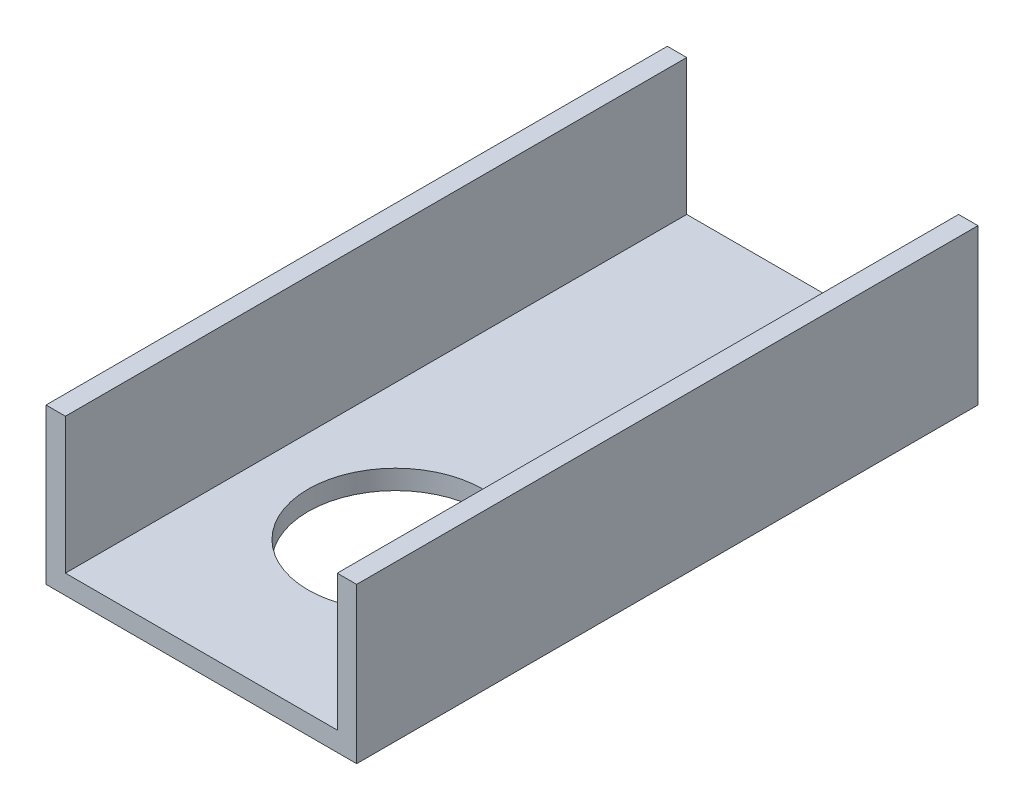
SolidWorks part; units mm, degrees
material "6063-T6"
ref_plane "Front" through (0, 0, 0) normal (0, 0, 1) x (1, 0, 0)
ref_plane "Top" through (0, 0, 0) normal (0, 1, 0) x (1, 0, 0)
ref_plane "Right" through (0, 0, 0) normal (1, 0, 0) x (0, 0, -1)
sketch "Sketch1" plane through (0, 0, 0) normal (0, 0, 1) x (1, 0, 0)
  line L0 (47.625, 3.175) -> (47.625, 25.4)
  line L1 (0, 0) -> (50.8, 0)
  line L2 (0, 0) -> (0, 25.4)
  line L4 (50.8, 0) -> (50.8, 25.4)
  line L5 (3.175, 3.175) -> (47.625, 3.175)
  line L6 (3.175, 3.175) -> (3.175, 25.4)
  line L7 (50.8, 25.4) -> (47.625, 25.4)
  line L8 (0, 25.4) -> (3.175, 25.4)
  dimension "D1" = 25.4
  dimension "D2" = 50.8
  dimension "D3" = 3.175
extrude "Boss-Extrude1" add sketch "Sketch1" along normal blind 101.6
sketch "Sketch2" plane through (0, 0, 0) normal (0, -1, 0) x (1, 0, 0)
  line L0 (25.4, 69.85) -> (25.4, 101.6) construction
  line L1 (0, 101.6) -> (50.8, 101.6) construction
  circle A0 centre (25.4, 69.85) radius 14.2875
  dimension "D1" = 28.575
  dimension "D2" = 31.75
extrude "Cut-Extrude1" cut sketch "Sketch2" against normal up to next
sketch "Sketch3" plane through (0, 3.175, 0) normal (0, 1, 0) x (1, 0, 0)
  line L1 (44.45, -22.225) -> (47.625, -22.225)
  line L2 (44.45, -22.225) -> (44.45, 0)
  line L3 (44.45, 0) -> (47.625, 0)
  line L4 (47.625, -22.225) -> (47.625, 0)
  line L5 (44.45, -22.225) -> (47.625, 0) construction
  line L6 (44.45, 0) -> (47.625, -22.225) construction
  line L8 (47.625, -101.6) -> (47.625, 0) construction
  line L9 (47.625, 0) -> (3.175, 0) construction
  point P4 (46.0375, -11.1125)
  point P7 (4.7625, -9.4119)
  point P8 (30.3637, -13.0946)
  dimension "D1" = 22.225
  dimension "D2" = 3.175
extrude "Cut-Extrude2" cut sketch "Sketch3" against normal up to next
